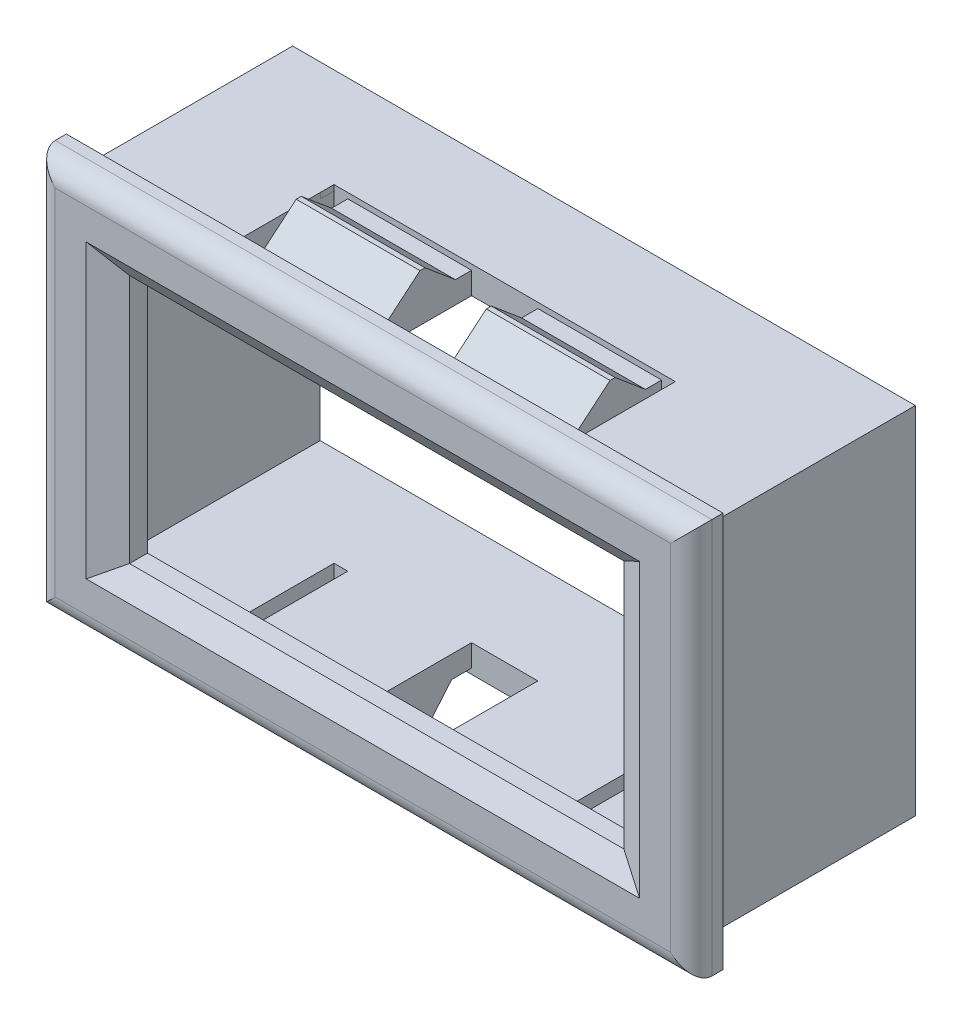
SolidWorks part; units mm, degrees
ref_plane "Plano frontal" through (0, 0, 0) normal (0, 0, 1) x (1, 0, 0)
ref_plane "Plano superior" through (0, 0, 0) normal (0, 1, 0) x (1, 0, 0)
ref_plane "Plano direito" through (0, 0, 0) normal (1, 0, 0) x (0, 0, -1)
sketch "Esboço1" plane through (0, 0, 0) normal (0, 0, 1) x (1, 0, 0)
  line L1 (23.875, -14.375) -> (-23.875, -14.375)
  line L2 (23.875, -14.375) -> (23.875, 14.375)
  line L3 (23.875, 14.375) -> (-23.875, 14.375)
  line L4 (-23.875, -14.375) -> (-23.875, 14.375)
  line L5 (23.875, -14.375) -> (-23.875, 14.375) construction
  line L6 (23.875, 14.375) -> (-23.875, -14.375) construction
  point P0 (0, 0)
  dimension "D1" = 47.75
  dimension "D2" = 28.75
extrude "Ressalto-extrusão1" add sketch "Esboço1" along normal blind 17.53
sketch "Esboço3" plane through (0, 0, 0) normal (0, 0, -1) x (-1, 0, 0)
  line L1 (-22.64, -12.925) -> (22.64, -12.925)
  line L2 (-22.64, -12.925) -> (-22.64, 12.925)
  line L3 (-22.64, 12.925) -> (22.64, 12.925)
  line L4 (22.64, -12.925) -> (22.64, 12.925)
  line L5 (-22.64, -12.925) -> (22.64, 12.925) construction
  line L6 (-22.64, 12.925) -> (22.64, -12.925) construction
  line L7 (-27.5567, -16.1162) -> (27.5567, -16.1162)
  line L8 (-27.5567, -16.1162) -> (-27.5567, 16.1162)
  line L9 (-27.5567, 16.1162) -> (27.5567, 16.1162)
  line L10 (27.5567, -16.1162) -> (27.5567, 16.1162)
  line L11 (-27.5567, -16.1162) -> (27.5567, 16.1162) construction
  line L12 (-27.5567, 16.1162) -> (27.5567, -16.1162) construction
  point P0 (0, 0)
  point P6 (0, 0)
  dimension "D1" = 25.85
  dimension "D2" = 45.28
extrude "Corte-extrusão1" cut sketch "Esboço3" against normal blind 15.22
sketch "Esboço4" plane through (0, 0, 17.53) normal (0, 0, 1) x (1, 0, 0)
  line L1 (-17.975, -9.07) -> (17.975, -9.07)
  line L2 (-17.975, -9.07) -> (-17.975, 9.07)
  line L3 (-17.975, 9.07) -> (17.975, 9.07)
  line L4 (17.975, -9.07) -> (17.975, 9.07)
  line L5 (-17.975, -9.07) -> (17.975, 9.07) construction
  line L6 (-17.975, 9.07) -> (17.975, -9.07) construction
  point P0 (0, 0)
  dimension "D1" = 18.14
  dimension "D2" = 35.95
extrude "Corte-extrusão2" cut sketch "Esboço4" against normal blind 33.22 and the other way blind 17
sketch "Esboço5" plane through (0, 0, 0) normal (0, 0, -1) x (-1, 0, 0)
  line L5 (20.64, -10.925) -> (-20.64, -10.925)
  line L6 (20.64, -10.925) -> (20.64, 10.925)
  line L7 (20.64, 10.925) -> (-20.64, 10.925)
  line L8 (-20.64, -10.925) -> (-20.64, 10.925)
  line L9 (20.64, -10.925) -> (-20.64, 10.925) construction
  line L10 (20.64, 10.925) -> (-20.64, -10.925) construction
  point P9 (0, 0)
extrude "Corte-extrusão3" cut sketch "Esboço5" against normal blind 15.22
chamfer "Chanfro1" distance 1 angle 65 1 edges at (17.975, 0, 17.53)
chamfer "Chanfro2" distance 1 angle 65 1 edges at (-17.975, 0, 17.53)
chamfer "Chanfro3" distance 1 angle 57 2 edges at (0, -9.07, 17.53) (0, 9.07, 17.53)
fillet "Filete1" radius 1.5 4 edges at (23.875, 0, 17.53) (-23.875, 0, 17.53) (0, -14.375, 17.53) (0, 14.375, 17.53)
sketch "Esboço6" plane through (0, 12.925, 0) normal (0, 1, 0) x (1, 0, 0)
  line L0 (-11.41, -7.8955) -> (-11.41, -7.22)
  line L2 (-22.64, -15.22) -> (22.64, -15.22) construction
  line L3 (-12.41, -7.22) -> (-11.41, -7.22)
  line L4 (-12.41, -7.22) -> (-12.41, -15.22)
  line L5 (-12.41, -15.22) -> (12.41, -15.22)
  line L6 (12.41, -7.22) -> (12.41, -15.22)
  line L7 (2.41, -14.5445) -> (11.41, -14.5445)
  line L8 (-2.41, -7.22) -> (2.41, -7.22)
  line L9 (2.41, -7.22) -> (2.41, -14.5445)
  line L10 (-11.41, -14.5445) -> (-2.41, -14.5445)
  line L11 (-11.41, -14.5445) -> (-11.41, -7.8955)
  line L12 (11.41, -7.22) -> (12.41, -7.22)
  line L13 (11.41, -14.5445) -> (11.41, -7.8955)
  line L16 (-2.41, -7.22) -> (-2.41, -14.5445)
  line L18 (11.41, -7.8955) -> (11.41, -7.22)
  point P5 (0, -11.22)
  point P12 (0, -11.22)
  dimension "D1" = 24.82
  dimension "D2" = 8
  dimension "D3" = 1
  dimension "D4" = 9
  dimension "D5" = 9
extrude "Corte-extrusão4" cut sketch "Esboço6" against normal blind 44.22 and the other way blind 15
sketch "Esboço7" plane through (0, 12.925, 0) normal (0, 1, 0) x (1, 0, 0)
  line L0 (-2.41, -7.22) -> (2.41, -7.22) construction
  line L1 (-12.4101, -8.22) -> (12.4101, -8.22)
  line L2 (12.4101, -8.22) -> (12.41, -7.22)
  line L3 (-12.4101, -8.22) -> (-12.41, -7.22)
  line L5 (-12.41, -7.22) -> (12.41, -7.22)
  point P0 (0, -7.22)
  dimension "D1" = 1
extrude "Corte-extrusão5" cut sketch "Esboço7" against normal blind 0.4
sketch "Esboço8" plane through (0, -12.925, 0) normal (0, -1, 0) x (1, 0, 0)
  line L0 (-12.41, 8.22) -> (12.41, 8.22)
  line L1 (12.41, 8.22) -> (12.41, 7.22)
  line L2 (12.41, 7.22) -> (-12.41, 7.22)
  line L3 (-12.41, 7.22) -> (-12.41, 8.22)
extrude "Corte-extrusão6" cut sketch "Esboço8" against normal blind 0.4
sketch "Esboço9" plane through (0, 12.925, 0) normal (0, 1, 0) x (1, 0, 0)
  line L2 (-11.41, -14.5445) -> (-2.41, -14.5445) construction
  line L3 (-2.41, -14.5445) -> (-2.41, -8.22) construction
  line L4 (-11.41, -8.22) -> (-2.41, -8.22)
  line L5 (-11.41, -8.22) -> (-11.41, -14.5445)
  line L6 (-11.41, -14.5445) -> (-2.41, -14.5445)
  line L7 (-2.41, -8.22) -> (-2.41, -14.5445)
  line L8 (-11.41, -8.22) -> (-2.41, -14.5445) construction
  line L9 (-11.41, -14.5445) -> (-2.41, -8.22) construction
  point P6 (-6.91, -11.3822)
extrude "Ressalto-extrusão2" add sketch "Esboço9" along normal blind 1.45
sketch "Esboço10" plane through (0, 12.925, 0) normal (0, 1, 0) x (1, 0, 0)
  line L4 (2.41, -14.5445) -> (11.41, -14.5445)
  line L5 (2.41, -14.5445) -> (2.41, -8.22)
  line L6 (2.41, -8.22) -> (11.41, -8.22)
  line L7 (11.41, -14.5445) -> (11.41, -8.22)
  line L8 (2.41, -14.5445) -> (11.41, -8.22) construction
  line L9 (2.41, -8.22) -> (11.41, -14.5445) construction
  point P6 (6.91, -11.3822)
extrude "Ressalto-extrusão3" add sketch "Esboço10" along normal blind 1.45
sketch "Esboço11" plane through (0, -12.925, 0) normal (0, -1, 0) x (1, 0, 0)
  line L3 (-6.91, 11.3822) -> (-6.91, 14.5445)
  line L5 (-2.41, 14.5445) -> (-11.41, 14.5445) construction
  line L7 (11.41, 14.5445) -> (2.41, 14.5445)
  line L8 (11.41, 14.5445) -> (11.41, 8.22)
  line L9 (11.41, 8.22) -> (2.41, 8.22)
  line L10 (2.41, 14.5445) -> (2.41, 8.22)
  line L11 (11.41, 14.5445) -> (2.41, 8.22) construction
  line L12 (11.41, 8.22) -> (2.41, 14.5445) construction
  line L13 (-2.41, 14.5445) -> (-11.41, 14.5445)
  line L14 (-2.41, 14.5445) -> (-2.41, 8.22)
  line L15 (-2.41, 8.22) -> (-11.41, 8.22)
  line L16 (-11.41, 14.5445) -> (-11.41, 8.22)
  line L17 (-2.41, 14.5445) -> (-11.41, 8.22) construction
  line L18 (-2.41, 8.22) -> (-11.41, 14.5445) construction
  point P12 (6.91, 11.3822)
  point P18 (-6.91, 11.3822)
extrude "Ressalto-extrusão4" add sketch "Esboço11" along normal blind 1.45
chamfer "Chanfro4" distance 3 angle 50 4 edges at (6.91, -14.375, 14.5445) (-6.91, -14.375, 14.5445) (-6.91, 14.375, 14.5445) (6.91, 14.375, 14.5445)
chamfer "Chanfro5" distance 2 angle 50 16 edges at (-2.41, 13.45, 8.22) (2.41, 13.45, 8.22) (-11.41, 13.45, 8.22) (11.41, 13.45, 8.22) (-6.91, 12.525, 8.22) (6.91, 12.525, 8.22) (-2.41, -13.45, 8.22) (2.41, -13.45, 8.22) (11.41, -13.45, 8.22) (-11.41, -13.45, 8.22) (6.91, -12.525, 8.22) (-6.91, -12.525, 8.22) (-6.91, 14.375, 8.22) (6.91, 14.375, 8.22) (6.91, -14.375, 8.22) (-6.91, -14.375, 8.22)
